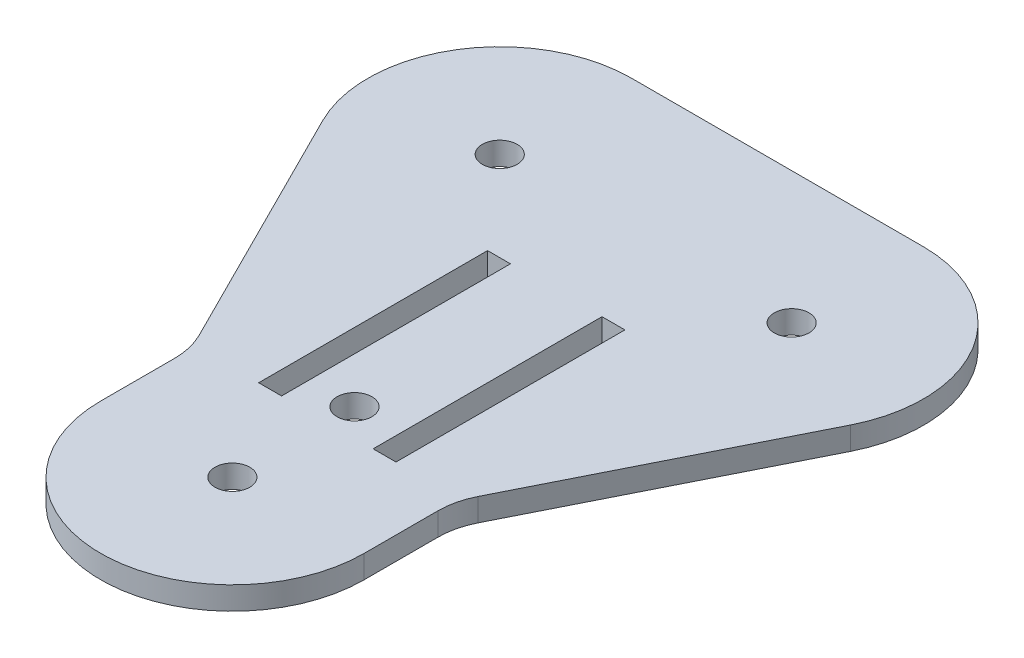
SolidWorks part; units mm, degrees
ref_plane "Front Plane" through (0, 0, 0) normal (0, 0, 1) x (1, 0, 0)
ref_plane "Top Plane" through (0, 0, 0) normal (0, 1, 0) x (1, 0, 0)
ref_plane "Right Plane" through (0, 0, 0) normal (1, 0, 0) x (0, 0, -1)
sketch "Sketch1" plane through (0, 0, 0) normal (0, 1, 0) x (1, 0, 0)
  line L0 (0, -16.9333) -> (0, 40.3963) construction
  line L1 (-20.2438, 40.3963) -> (20.2438, 40.3963) construction
  line L10 (-36.5937, 32.2029) -> (-16.3499, -8.1934)
  line L11 (16.3499, -8.1934) -> (36.5937, 32.2029)
  line L12 (-18.288, 0) -> (-18.288, -16.9333)
  line L13 (18.288, 0) -> (18.288, -16.9333)
  line L14 (-20.2438, 58.6843) -> (20.2438, 58.6843)
  circle A0 centre (0, -16.9333) radius 2.413
  circle A1 centre (20.2438, 40.3963) radius 2.413
  circle A2 centre (-20.2438, 40.3963) radius 2.413
  circle A6 centre (0, 0) radius 2.413
  circle A7 centre (-20.2438, 40.3963) radius 18.288
  circle A8 centre (20.2438, 40.3963) radius 18.288
  circle A9 centre (0, 0) radius 18.288
  circle A10 centre (0, -16.9333) radius 18.288
  point P1 (0, 40.3963)
  dimension "D2" = 4.826
  dimension "D1" = 15.875
  dimension "D3" = 40.4876
  dimension "D4" = 40.3963
  dimension "D5" = 16.9333
extrude "Boss-Extrude1" add sketch "Sketch1" along normal blind 3.175 contours A9 L12 L10 | A10 A9 L10 L12 | A9 L11 L13 | A10 L13 L11 A9 | A10 A9 A0 | A9 A10 | A10 A9 A6 | A9 L13 L11 A8 L14 A7 L10 L12 | A7 A2 | A8 A1 region at (0, 0, -25.2451) region at (-35.3647, 0, -49.7321) region at (-17.8968, 0, 4.2334) region at (-17.6391, 0, 9.0699) region at (0, 0, -6.4727) region at (0, 0, 23.4061) region at (32.8096, 0, -52.9621) region at (0, 0, 8.4667) region at (17.8968, 0, 4.2334) region at (17.6391, 0, 9.0699)
fillet "Fillet1" radius 10 2 edges at (18.288, 1.5875, 4.3259) (-18.288, 1.5875, 4.3259)
sketch "Sketch2" plane through (0, 3.175, 0) normal (0, 1, 0) x (1, 0, 0)
  line L0 (0, -16.9333) -> (0, 58.6843) construction
  line L1 (9.525, -3.7615) -> (6.35, -3.7615)
  line L2 (-9.525, 27.9885) -> (-6.35, 27.9885)
  line L3 (-9.525, 27.9885) -> (-9.525, -3.7615)
  line L4 (-9.525, -3.7615) -> (-6.35, -3.7615)
  line L5 (18.288, -16.9333) -> (18.288, -6.6914)
  line L6 (19.3478, -2.2112) -> (36.5937, 32.2029)
  line L7 (20.2438, 58.6843) -> (-20.2438, 58.6843)
  line L8 (-36.5937, 32.2029) -> (-19.3478, -2.2112)
  line L9 (-18.288, -6.6914) -> (-18.288, -16.9333)
  line L10 (18.288, -16.9333) -> (18.288, -6.6914)
  line L11 (19.3478, -2.2112) -> (36.5937, 32.2029)
  line L12 (20.2438, 58.6843) -> (-20.2438, 58.6843)
  line L13 (-36.5937, 32.2029) -> (-19.3478, -2.2112)
  line L14 (-18.288, -6.6914) -> (-18.288, -16.9333)
  line L15 (-6.35, 27.9885) -> (-6.35, -3.7615)
  line L16 (6.35, 27.9885) -> (6.35, -3.7615)
  line L17 (9.525, 27.9885) -> (6.35, 27.9885)
  line L18 (9.525, 27.9885) -> (9.525, -3.7615)
  line L19 (-20.2438, 58.6843) -> (20.2438, 58.6843) construction
  arc A5 (19.3478, -2.2112) -> (18.288, -6.6914) centre (28.288, -6.6914) ccw
  arc A6 (36.5937, 32.2029) -> (20.2438, 58.6843) centre (20.2438, 40.3963) ccw
  arc A7 (-20.2438, 58.6843) -> (-36.5937, 32.2029) centre (-20.2438, 40.3963) ccw
  arc A8 (-18.288, -6.6914) -> (-19.3478, -2.2112) centre (-28.288, -6.6914) ccw
  arc A9 (-18.288, -16.9333) -> (18.288, -16.9333) centre (0, -16.9333) ccw
  arc A10 (19.3478, -2.2112) -> (18.288, -6.6914) centre (28.288, -6.6914) ccw
  arc A11 (36.5937, 32.2029) -> (20.2438, 58.6843) centre (20.2438, 40.3963) ccw
  arc A12 (-20.2438, 58.6843) -> (-36.5937, 32.2029) centre (-20.2438, 40.3963) ccw
  arc A13 (-18.288, -6.6914) -> (-19.3478, -2.2112) centre (-28.288, -6.6914) ccw
  arc A14 (-18.288, -16.9333) -> (18.288, -16.9333) centre (0, -16.9333) ccw
  point P24 (0, 52.3343)
  dimension "D2" = 31.75
  dimension "D3" = 12.7
  dimension "D4" = 3.175
  dimension "D5" = 30.6958
  dimension "D1" = 0
extrude "Cut-Extrude1" cut sketch "Sketch2" against normal up to next contours L15 L2 L3 L4 | L18 L17 L16 L1 region at (7.9375, 3.175, -12.1135) region at (-7.9375, 3.175, -12.1135)
